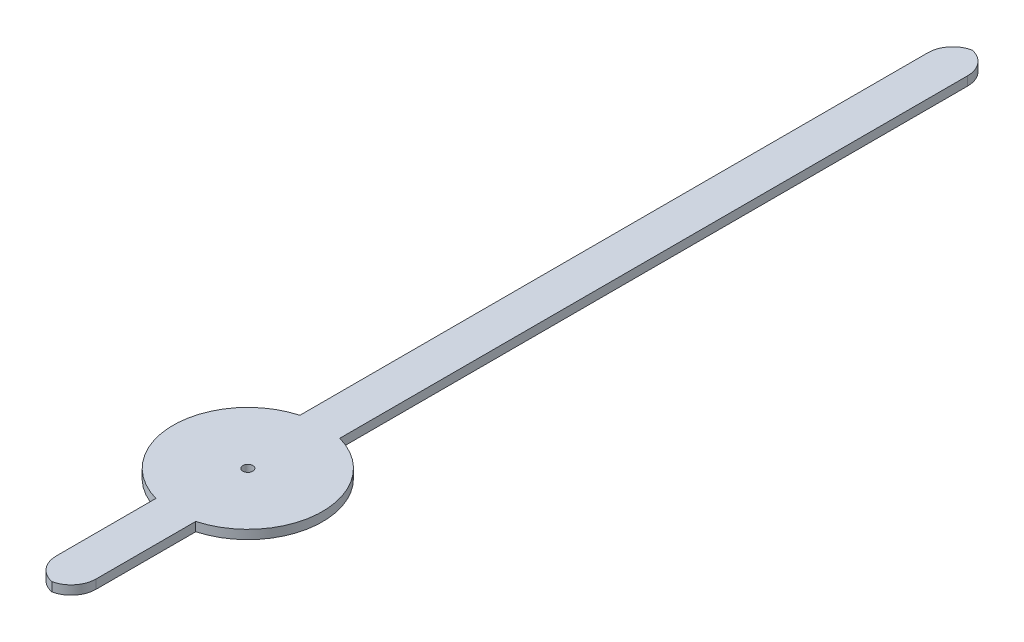
SolidWorks part; units mm, degrees
ref_plane "Front Plane" through (0, 0, 0) normal (0, 0, 1) x (1, 0, 0)
ref_plane "Top Plane" through (0, 0, 0) normal (0, 1, 0) x (1, 0, 0)
ref_plane "Right Plane" through (0, 0, 0) normal (1, 0, 0) x (0, 0, -1)
sketch "Sketch1" plane through (0, 0, 0) normal (0, 1, 0) x (1, 0, 0)
  line L0 (0, 0) -> (-0.1, 0) construction
  line L1 (-0.4, -3.9457) -> (-0.4, -1.4457)
  line L3 (0, -55) -> (0, 55) construction
  line L4 (0.4, -3.9457) -> (0.4, -1.4457)
  line L5 (0.4, 1.4457) -> (0.4, 14.5543)
  line L6 (-0.4, -3.9457) -> (0.4, -3.9457)
  line L7 (-0.4, 14.5543) -> (0.4, 14.5543)
  line L8 (-0.4, 1.4457) -> (-0.4, 14.5543)
  circle A0 centre (0, 0) radius 0.1
  arc A1 (-0.4, 1.4457) -> (-0.4, -1.4457) centre (0, 0) ccw
  arc A2 (0.4, -1.4457) -> (0.4, 1.4457) centre (0, 0) ccw
  dimension "D1" = 0.2
  dimension "D2" = 3
  dimension "D3" = 2.5
  dimension "D4" = 0.4
  dimension "D5" = 18.5
extrude "Boss-Extrude2" add sketch "Sketch1" along normal blind 0.18
fillet "Fillet1" radius 0.5 4 edges at (-0.4, 0.09, -14.5543) (0.4, 0.09, -14.5543) (-0.4, 0.09, 3.9457) (0.4, 0.09, 3.9457)
